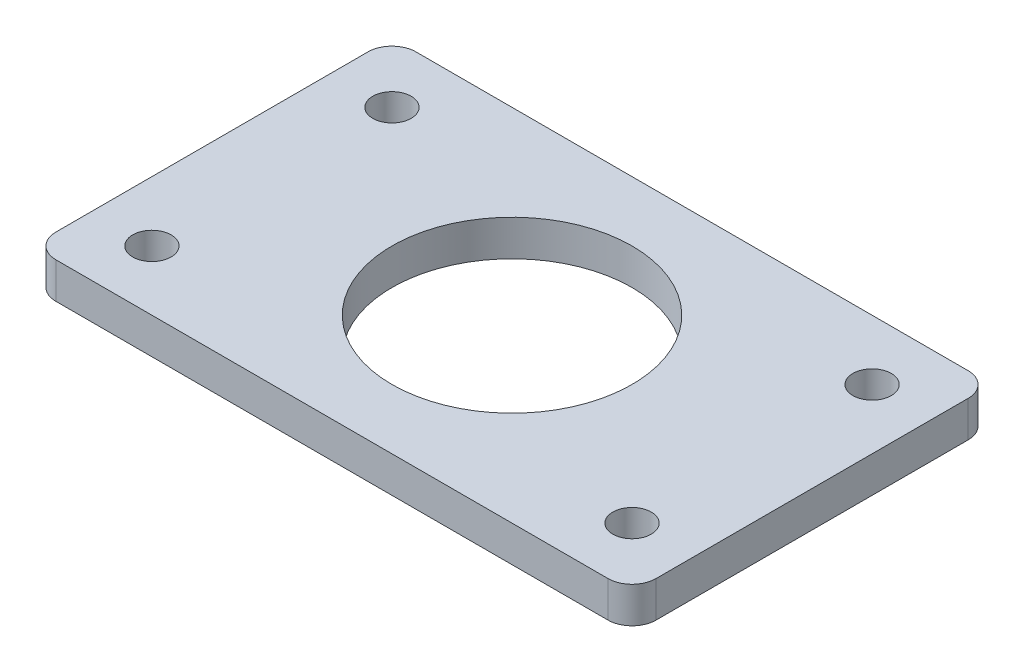
SolidWorks part; units mm, degrees
material "AISI 1045 Steel, cold drawn"
ref_plane "Front Plane" through (0, 0, 0) normal (0, 0, 1) x (1, 0, 0)
ref_plane "Top Plane" through (0, 0, 0) normal (0, 1, 0) x (1, 0, 0)
ref_plane "Right Plane" through (0, 0, 0) normal (1, 0, 0) x (0, 0, -1)
sketch "Sketch1" plane through (0, 0, 0) normal (0, 1, 0) x (1, 0, 0)
  line L1 (25, -15) -> (-25, -15)
  line L2 (25, -15) -> (25, 15)
  line L3 (25, 15) -> (-25, 15)
  line L4 (-25, -15) -> (-25, 15)
  line L5 (25, -15) -> (-25, 15) construction
  line L6 (25, 15) -> (-25, -15) construction
  circle A0 centre (0, 0) radius 10
  dimension "D1" = 20
  dimension "D2" = 30
  dimension "D3" = 50
extrude "Boss-Extrude1" add sketch "Sketch1" along normal blind 3
hole_wizard "M3 Clearance Hole1" positions "Sketch4" profile "Sketch3" hole size "M3" standard "ANSI Metric" end condition up to next
sketch "Sketch4" plane through (0, 3, 0) normal (0, 1, 0) x (1, 0, 0)
  line L1 (20, -10) -> (-20, -10)
  line L2 (20, -10) -> (20, 10)
  line L3 (20, 10) -> (-20, 10)
  line L4 (-20, -10) -> (-20, 10)
  line L5 (20, -10) -> (-20, 10) construction
  line L6 (20, 10) -> (-20, -10) construction
  line L7 (25, -15) -> (25, 15) construction
  line L8 (25, 15) -> (-25, 15) construction
  point P1 (0, 0)
  point P2 (-20, 10)
  point P119 (20, -10)
  point P120 (20, 10)
  point P121 (-20, -10)
  dimension "D1" = 5
  dimension "D2" = 5
sketch "Sketch3" plane through (0, 3, 0) normal (1, 0, 0) x (0, 0, 1)
  line L0 (0, 0) -> (0, 3)
  line L1 (0, 3) -> (1.6, 3)
  line L2 (1.6, 3) -> (1.6, 0)
  line L5 (1.6, 0) -> (0, 0)
  line L11 (0, -6.35) -> (0, 107.95) construction
  dimension "Thru Hole Dia." = 3.2
  dimension "Thru Hole Depth" = 3
fillet "Fillet1" radius 2 4 edges at (-25, 1.5, -15) (25, 1.5, -15) (25, 1.5, 15) (-25, 1.5, 15)
